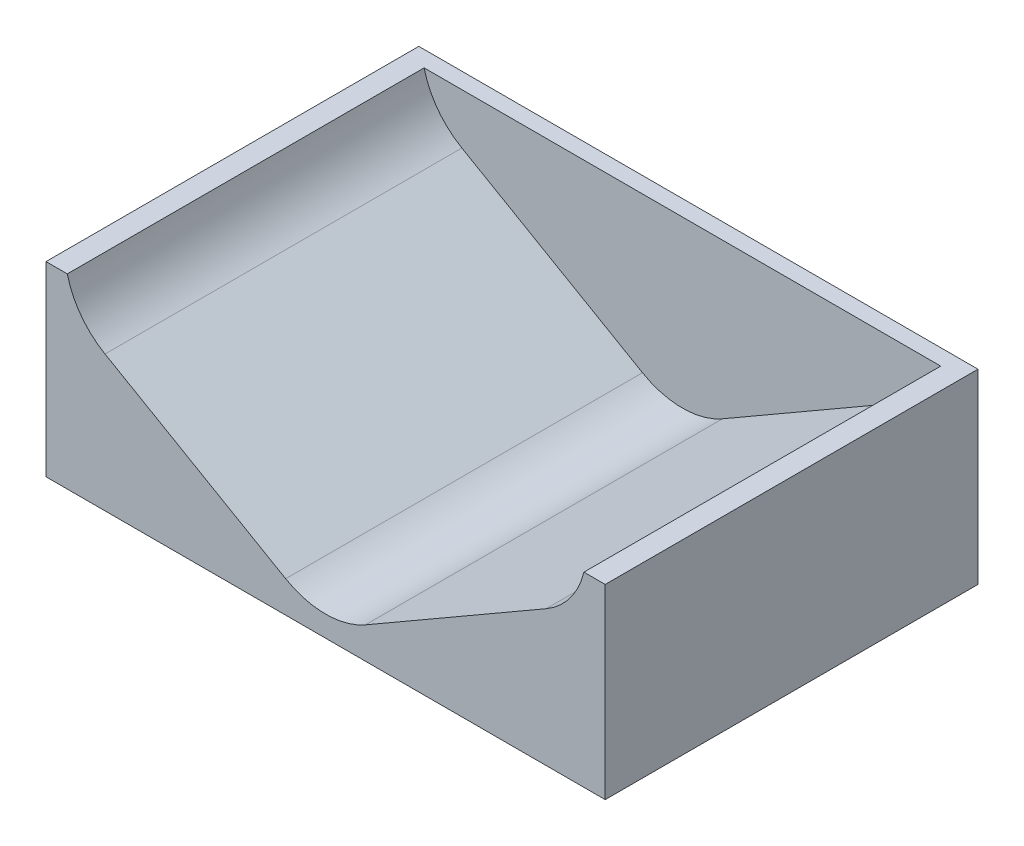
SolidWorks part; units mm, degrees
ref_plane "Plan de face" through (0, 0, 0) normal (0, 0, 1) x (1, 0, 0)
ref_plane "Plan de dessus" through (0, 0, 0) normal (0, 1, 0) x (1, 0, 0)
ref_plane "Plan de droite" through (0, 0, 0) normal (1, 0, 0) x (0, 0, -1)
sketch "Esquisse1" plane through (0, 0, 0) normal (0, 0, 1) x (1, 0, 0)
  line L0 (0, 0) -> (48.5, 28.0015)
  line L2 (52.5, -1.6) -> (-52.5, -1.6)
  line L4 (-48.5, 28.0015) -> (0, 0)
  line L5 (-48.5, 28.0015) -> (-48.5, 33.4)
  line L6 (-48.5, 33.4) -> (-52.5, 33.4)
  line L7 (-52.5, 33.4) -> (-52.5, -1.6)
  line L8 (48.5, 28.0015) -> (48.5, 33.4)
  line L9 (48.5, 33.4) -> (52.5, 33.4)
  line L10 (52.5, 33.4) -> (52.5, -1.6)
  point P12 (0, -1.6)
  dimension "D1" = 120
  dimension "D2" = 105
  dimension "D3" = 1.6
  dimension "D4" = 97
  dimension "D6" = 35
extrude "Boss.-Extru.1" add sketch "Esquisse1" along normal blind 70
fillet "Congé1" radius 15 3 edges at (0, 0, 35) (48.5, 28.0015, 35) (-48.5, 28.0015, 35)
sketch "Esquisse2" plane through (0, 0, 0) normal (0, 0, 1) x (1, 0, 0)
  line L1 (-52.5, -1.6) -> (52.5, -1.6)
  line L2 (-52.5, -1.6) -> (-52.5, 33.4)
  line L3 (-52.5, 33.4) -> (52.5, 33.4)
  line L4 (52.5, -1.6) -> (52.5, 33.4)
extrude "Boss.-Extru.2" add sketch "Esquisse2" along normal blind 3
